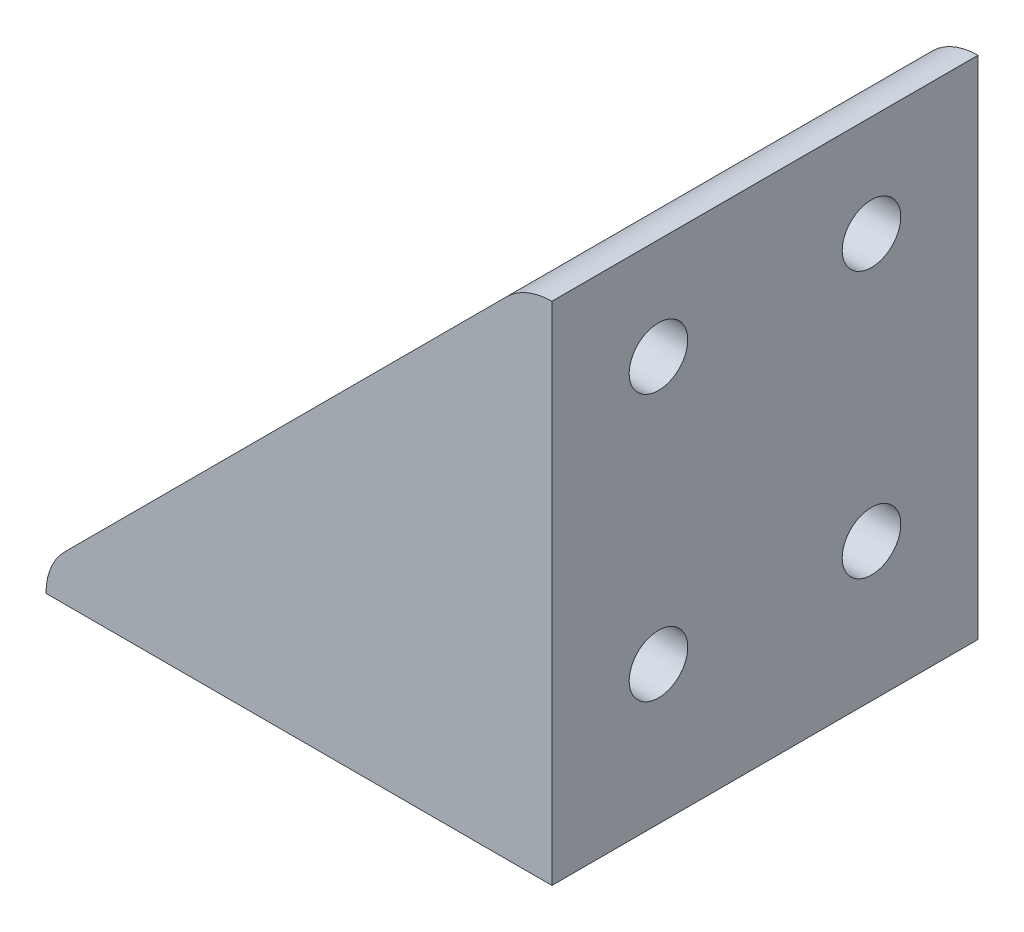
SolidWorks part; units mm, degrees
ref_plane "Front Plane" through (0, 0, 0) normal (0, 0, 1) x (1, 0, 0)
ref_plane "Top Plane" through (0, 0, 0) normal (0, 1, 0) x (1, 0, 0)
ref_plane "Right Plane" through (0, 0, 0) normal (1, 0, 0) x (0, 0, -1)
sketch "Sketch1" plane through (0, 0, 0) normal (0, 1, 0) x (1, 0, 0)
  line L1 (-25, -20) -> (25, -20)
  line L2 (-25, -20) -> (-25, 20)
  line L3 (-25, 20) -> (25, 20)
  line L4 (25, -20) -> (25, 20)
  line L5 (-25, -20) -> (25, 20) construction
  line L6 (-25, 20) -> (25, -20) construction
  point P0 (0, 0)
  dimension "D1" = 50
  dimension "D2" = 40
extrude "Boss-Extrude1" add sketch "Sketch1" along normal blind 50
sketch "Sketch2" plane through (0, 0, 20) normal (0, 0, 1) x (1, 0, 0)
  line L0 (-25, 0) -> (25, 50)
  line L1 (25, 50) -> (-25, 50)
  line L2 (-25, 50) -> (-25, 0)
extrude "Cut-Extrude1" cut sketch "Sketch2" against normal through all
shell "Shell1" thickness 5 removed face at (0, 25, 0)
hole_wizard "M5 Clearance Hole1" positions "Sketch3" profile "Sketch4" hole size "M5" standard "ANSI Metric"
sketch "Sketch3" plane through (20, 0, 0) normal (-1, 0, 0) x (0, 0, 1)
  line L0 (20, 50) -> (20, 0) construction
  line L1 (-20, 50) -> (-20, 0) construction
  line L2 (20, 50) -> (20, 0)
  line L3 (-20, 50) -> (-20, 0)
  line L4 (15, 5) -> (-15, 5) construction
  point P0 (-10, 38)
  point P2 (-10, 13)
  point P4 (10, 13)
  point P6 (10, 38)
  dimension "D1" = 8
  dimension "D2" = 20
  dimension "D3" = 10
  dimension "D4" = 25
sketch "Sketch4" plane through (20, 38, -10) normal (0, 1, 0) x (0, 0, 1)
  line L0 (0, 0) -> (0, 13.6524)
  line L1 (0, 13.6524) -> (2.75, 12)
  line L2 (2.75, 12) -> (2.75, 0)
  line L5 (2.75, 0) -> (0, 0)
  line L10 (0, 13.6524) -> (-2.75, 12) construction
  line L11 (0, -6.35) -> (0, 107.95) construction
  dimension "Hole Dia." = 5.5
  dimension "Hole Depth" = 12
  dimension "Drill Angle" = 118
sketch "Sketch5" plane through (0, 0, -15) normal (0, 0, 1) x (1, 0, 0)
  line L3 (-20, 5) -> (20, 5)
  line L4 (20, 5) -> (20, 45)
  line L5 (20, 45) -> (-20, 5)
  line L6 (-20, 5) -> (20, 5)
  line L7 (20, 5) -> (20, 45)
  line L8 (20, 45) -> (-20, 5)
  dimension "D1" = 0
extrude "Cut-Extrude2" cut sketch "Sketch5" against normal blind 1
sketch "Sketch6" plane through (0, 0, 15) normal (0, 0, -1) x (-1, 0, 0)
  line L3 (-20, 45) -> (-20, 5)
  line L4 (-20, 5) -> (20, 5)
  line L5 (20, 5) -> (-20, 45)
  line L6 (-20, 45) -> (-20, 5)
  line L7 (-20, 5) -> (20, 5)
  line L8 (20, 5) -> (-20, 45)
  dimension "D1" = 0
extrude "Cut-Extrude3" cut sketch "Sketch6" against normal blind 1
sketch "Sketch7" plane through (0, 0, 20) normal (0, 0, 1) x (1, 0, 0)
  line L0 (-22.5, 2.5) -> (-22.5, 0)
  line L1 (-25, 0) -> (25, 50) construction
  line L2 (-25, 0) -> (25, 0) construction
  line L3 (22.5, 47.5) -> (25, 47.5)
  line L4 (25, 50) -> (25, 0) construction
  line L5 (-22.5, 2.5) -> (-25, 0)
  line L6 (-25, 0) -> (-22.5, 0)
  line L7 (22.5, 47.5) -> (25, 50)
  line L8 (25, 50) -> (25, 47.5)
  dimension "D1" = 2.5
  dimension "D2" = 2.5
extrude "Cut-Extrude4" cut sketch "Sketch7" against normal through all
fillet "Fillet2" radius 6 2 edges at (-22.5, 2.5, 0) (22.5, 47.5, 0)
hole_wizard "M5 Clearance Hole2" positions "Sketch8" profile "Sketch9" hole size "M5" standard "ANSI Metric"
sketch "Sketch8" plane through (0, 5, 0) normal (0, 1, 0) x (1, 0, 0)
  line L0 (-22.5, -20) -> (25, -20) construction
  line L1 (20, -16) -> (20, 16) construction
  point P0 (12, 10)
  point P2 (12, -10)
  point P4 (-13, 10)
  point P6 (-13, -10)
  dimension "D1" = 10
  dimension "D2" = 20
  dimension "D3" = 25
  dimension "D4" = 8
sketch "Sketch9" plane through (12, 5, -10) normal (1, 0, 0) x (0, 0, 1)
  line L0 (0, 0) -> (0, 13.6524)
  line L1 (0, 13.6524) -> (2.75, 12)
  line L2 (2.75, 12) -> (2.75, 0)
  line L5 (2.75, 0) -> (0, 0)
  line L10 (0, 13.6524) -> (-2.75, 12) construction
  line L11 (0, -6.35) -> (0, 107.95) construction
  dimension "Hole Dia." = 5.5
  dimension "Hole Depth" = 12
  dimension "Drill Angle" = 118
sketch "Sketch10" plane through (0, 0, 0) normal (0, 0, 1) x (1, 0, 0)
  line L0 (-20.7426, 4.2574) -> (-20, 5)
  line L1 (20, 45) -> (20.7426, 45.7426)
  line L2 (20, 45) -> (20.7426, 45.7426)
  line L3 (-20.7426, 4.2574) -> (-20, 5)
  line L4 (20, 45) -> (20, 5)
  line L5 (20, 45) -> (20, 5)
  line L6 (-20, 5) -> (20, 5)
  line L7 (-20, 5) -> (20, 5)
  line L8 (20, 45) -> (-20, 5)
extrude "Boss-Extrude2" add sketch "Sketch10" along normal blind 2 and the other way blind 2 contours L5 L8 L7 region at (6.6667, 18.3333, 0)
